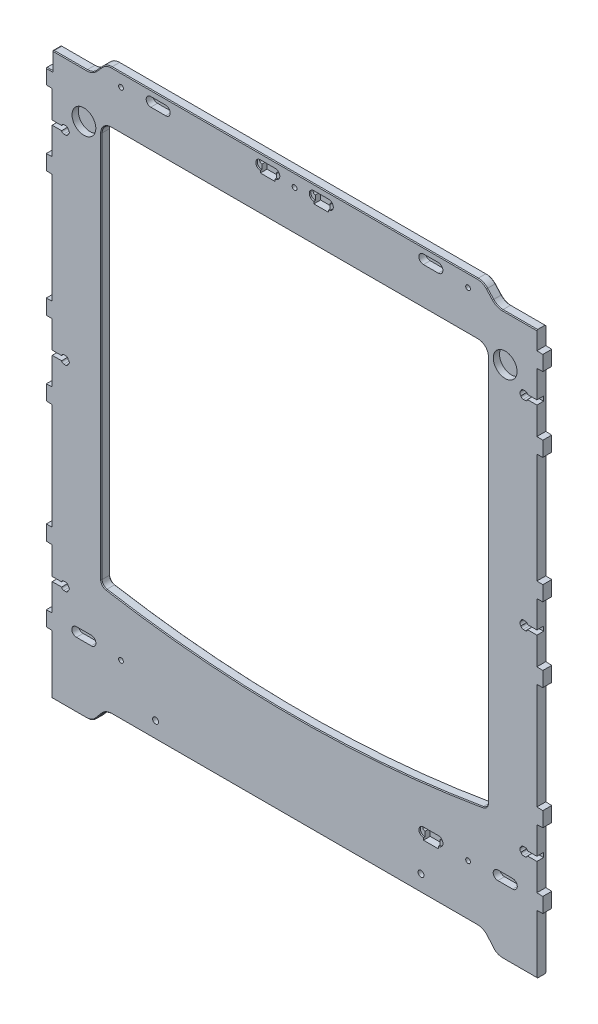
SolidWorks part; units mm, degrees
ref_plane "Alzado" through (0, 0, 0) normal (0, 0, 1) x (1, 0, 0)
ref_plane "Planta" through (0, 0, 0) normal (0, 1, 0) x (1, 0, 0)
ref_plane "Vista lateral" through (0, 0, 0) normal (1, 0, 0) x (0, 0, -1)
ref_plane "Plano1" through (0, 0, 3) normal (0, 0, 1) x (1, 0, 0)
sketch "Croquis1" plane through (0, 0, 3) normal (0, 0, 1) x (1, 0, 0)
  line L0 (167.1, -194) -> (167.1, 194)
  line L1 (167.1, 194) -> (-167.1, 194)
  line L2 (-167.1, 194) -> (-167.1, -194)
  line L3 (-167.1, -194) -> (167.1, -194)
  dimension "D1" = 334.2
  dimension "D2" = 388
extrude "Saliente-Extruir1" add sketch "Croquis1" against normal blind 6
sketch "Croquis2" plane through (0, 0, 3) normal (0, 0, 1) x (1, 0, 0)
  line L0 (96.8, -151.6) -> (96.8, -150.1)
  line L1 (96.8, -143.9) -> (86.8, -143.9)
  line L2 (86.8, -150.1) -> (86.8, -151.6)
  line L3 (86.8, -151.6) -> (96.8, -151.6)
  line L5 (-167.1, -194) -> (167.1, -194) construction
  arc A0 (96.8, -150.1) -> (96.8, -143.9) centre (96.8, -147) ccw
  arc A1 (86.8, -143.9) -> (86.8, -150.1) centre (86.8, -147) ccw
  dimension "D1" = 3.1
  dimension "D2" = 3.1
  dimension "D3" = 42.4
extrude "Cortar-Extruir1" cut sketch "Croquis2" against normal blind 1
sketch "Croquis3" plane through (0, 0, 2) normal (0, 0, 1) x (1, 0, 0)
  line L0 (86.8, -146.9) -> (86.8, -151.6)
  line L1 (86.8, -151.6) -> (96.8, -151.6)
  line L2 (96.8, -151.6) -> (96.8, -146.9)
  line L3 (96.8, -143.9) -> (86.8, -143.9)
  line L4 (96.8, -151.6) -> (96.8, -150.1) construction
  arc A0 (86.8, -143.9) -> (86.8, -146.9) centre (86.8, -145.4) ccw
  arc A1 (96.8, -146.9) -> (96.8, -143.9) centre (96.8, -145.4) ccw
  dimension "D1" = 1.5
  dimension "D2" = 10
extrude "Cortar-Extruir2" cut sketch "Croquis3" against normal blind 3.5
sketch "Croquis4" plane through (0, 0, 3) normal (0, 0, 1) x (1, 0, 0)
  line L0 (-13, 182.4) -> (-13, 183.9)
  line L1 (-13, 190.1) -> (-23, 190.1)
  line L2 (-23, 183.9) -> (-23, 182.4)
  line L3 (-23, 182.4) -> (-13, 182.4)
  line L4 (86.8, -150.1) -> (86.8, -151.6) construction
  line L5 (86.8, -151.6) -> (96.8, -151.6) construction
  arc A0 (-13, 183.9) -> (-13, 190.1) centre (-13, 187) ccw
  arc A1 (-23, 190.1) -> (-23, 183.9) centre (-23, 187) ccw
  dimension "D1" = 3.1
  dimension "D2" = 99.8
  dimension "D3" = 109.8
  dimension "D4" = 334
  dimension "D5" = 338.6
extrude "Cortar-Extruir3" cut sketch "Croquis4" against normal blind 1
sketch "Croquis5" plane through (0, 0, 2) normal (0, 0, 1) x (1, 0, 0)
  line L0 (-23, 187.1) -> (-23, 182.4)
  line L1 (-23, 182.4) -> (-13, 182.4)
  line L2 (-13, 182.4) -> (-13, 187.1)
  line L3 (-13, 190.1) -> (-23, 190.1)
  line L4 (-13, 182.4) -> (-13, 183.9) construction
  arc A0 (-23, 190.1) -> (-23, 187.1) centre (-23, 188.6) ccw
  arc A1 (-13, 187.1) -> (-13, 190.1) centre (-13, 188.6) ccw
  dimension "D1" = 1.5
  dimension "D2" = 10
extrude "Cortar-Extruir4" cut sketch "Croquis5" against normal blind 3.5
sketch "Croquis6" plane through (0, 0, -3) normal (0, 0, -1) x (-1, 0, 0)
  line L0 (167.1, 121.8397) -> (167.1, 161.5603)
  line L1 (167.1, 161.5603) -> (163.1, 161.5603)
  line L2 (163.1, 161.5603) -> (163.1, 121.8397)
  line L3 (163.1, 121.8397) -> (167.1, 121.8397)
  line L4 (167.1, 194) -> (167.1, -194) construction
  line L5 (167.1, -194) -> (-167.1, -194) construction
  dimension "D1" = 4
  dimension "D2" = 315.8397
  dimension "D3" = 355.5603
extrude "Cortar-Extruir5" cut sketch "Croquis6" against normal through all
sketch "Croquis7" plane through (0, 0, -3) normal (0, 0, -1) x (-1, 0, 0)
  line L0 (167.1, -12.3603) -> (167.1, 27.3603)
  line L1 (167.1, 27.3603) -> (163.1, 27.3603)
  line L2 (163.1, 27.3603) -> (163.1, -12.3603)
  line L3 (163.1, -12.3603) -> (167.1, -12.3603)
  line L4 (163.1, 161.5603) -> (163.1, 121.8397) construction
  line L5 (167.1, 161.5603) -> (163.1, 161.5603) construction
  dimension "D1" = 4
  dimension "D2" = 134.2
  dimension "D3" = 173.9206
extrude "Cortar-Extruir6" cut sketch "Croquis7" against normal through all
sketch "Croquis8" plane through (0, 0, -3) normal (0, 0, -1) x (-1, 0, 0)
  line L0 (167.1, -144.0603) -> (167.1, -104.3397)
  line L1 (167.1, -104.3397) -> (163.1, -104.3397)
  line L2 (163.1, -104.3397) -> (163.1, -144.0603)
  line L3 (163.1, -144.0603) -> (167.1, -144.0603)
  line L4 (167.1, 121.8397) -> (167.1, 27.3603) construction
  line L5 (163.1, 121.8397) -> (167.1, 121.8397) construction
  dimension "D1" = 4
  dimension "D2" = 226.1794
  dimension "D3" = 265.9
extrude "Cortar-Extruir7" cut sketch "Croquis8" against normal through all
sketch "Croquis9" plane through (0, 0, 3) normal (0, 0, 1) x (1, 0, 0)
  line L0 (-163.1, -125.8) -> (-156.779, -125.8)
  line L1 (-155.3, -127.05) -> (-153.9, -127.05)
  line L2 (-152.421, -125.8) -> (-152.421, -125.6375)
  line L3 (-152.421, -122.9625) -> (-152.421, -122.8)
  line L4 (-153.9, -121.55) -> (-155.3, -121.55)
  line L5 (-156.779, -122.8) -> (-163.1, -122.8)
  line L6 (-163.1, -122.8) -> (-163.1, -125.8)
  line L7 (-167.1, -144.0603) -> (-167.1, -194) construction
  line L8 (-167.1, -194) -> (167.1, -194) construction
  arc A0 (-156.779, -125.8) -> (-155.3, -127.05) centre (-155.3, -125.55) ccw
  arc A1 (-153.9, -127.05) -> (-152.421, -125.8) centre (-153.9, -125.55) ccw
  arc A2 (-152.421, -125.6375) -> (-152.421, -122.9625) centre (-153.1, -124.3) ccw
  arc A3 (-152.421, -122.8) -> (-153.9, -121.55) centre (-153.9, -123.05) ccw
  arc A4 (-155.3, -121.55) -> (-156.779, -122.8) centre (-155.3, -123.05) ccw
  dimension "D1" = 1.5
  dimension "D2" = 1.5
  dimension "D3" = 1.5
  dimension "D4" = 4
  dimension "D5" = 10.321
  dimension "D6" = 11.8
  dimension "D7" = 13.2
  dimension "D8" = 14
  dimension "D9" = 68.3625
extrude "Cortar-Extruir8" cut sketch "Croquis9" against normal blind 4.5
sketch "Croquis10" plane through (0, 0, 3) normal (0, 0, 1) x (1, 0, 0)
  line L0 (-163.1, 6.1) -> (-156.779, 6.1)
  line L1 (-155.3, 4.85) -> (-153.9, 4.85)
  line L2 (-152.421, 6.1) -> (-152.421, 6.2625)
  line L3 (-152.421, 8.9375) -> (-152.421, 9.1)
  line L4 (-153.9, 10.35) -> (-155.3, 10.35)
  line L5 (-156.779, 9.1) -> (-163.1, 9.1)
  line L6 (-163.1, 9.1) -> (-163.1, 6.1)
  line L7 (-167.1, -144.0603) -> (-167.1, -194) construction
  line L8 (-167.1, -194) -> (167.1, -194) construction
  arc A0 (-156.779, 6.1) -> (-155.3, 4.85) centre (-155.3, 6.35) ccw
  arc A1 (-153.9, 4.85) -> (-152.421, 6.1) centre (-153.9, 6.35) ccw
  arc A2 (-152.421, 6.2625) -> (-152.421, 8.9375) centre (-153.1, 7.6) ccw
  arc A3 (-152.421, 9.1) -> (-153.9, 10.35) centre (-153.9, 8.85) ccw
  arc A4 (-155.3, 10.35) -> (-156.779, 9.1) centre (-155.3, 8.85) ccw
  dimension "D1" = 1.5
  dimension "D2" = 1.5
  dimension "D3" = 1.5
  dimension "D4" = 4
  dimension "D5" = 200.2625
  dimension "D6" = 201.6
  dimension "D8" = 14
extrude "Cortar-Extruir9" cut sketch "Croquis10" against normal blind 4.5
sketch "Croquis11" plane through (0, 0, 3) normal (0, 0, 1) x (1, 0, 0)
  line L0 (-163.1, 140.2) -> (-156.779, 140.2)
  line L1 (-155.3, 138.95) -> (-153.9, 138.95)
  line L2 (-152.421, 140.2) -> (-152.421, 140.3625)
  line L3 (-152.421, 143.0375) -> (-152.421, 143.2)
  line L4 (-153.9, 144.45) -> (-155.3, 144.45)
  line L5 (-156.779, 143.2) -> (-163.1, 143.2)
  line L6 (-163.1, 143.2) -> (-163.1, 140.2)
  line L7 (-167.1, -12.3603) -> (-167.1, -104.3397) construction
  line L8 (-155.3, -127.05) -> (-153.9, -127.05) construction
  arc A0 (-156.779, 140.2) -> (-155.3, 138.95) centre (-155.3, 140.45) ccw
  arc A1 (-153.9, 138.95) -> (-152.421, 140.2) centre (-153.9, 140.45) ccw
  arc A2 (-152.421, 140.3625) -> (-152.421, 143.0375) centre (-153.1, 141.7) ccw
  arc A3 (-152.421, 143.2) -> (-153.9, 144.45) centre (-153.9, 142.95) ccw
  arc A4 (-155.3, 144.45) -> (-156.779, 143.2) centre (-155.3, 142.95) ccw
  dimension "D1" = 1.5
  dimension "D2" = 1.5
  dimension "D3" = 1.5
  dimension "D4" = 4
  dimension "D5" = 266
  dimension "D6" = 267.25
  dimension "D7" = 267.4125
  dimension "D8" = 14
  dimension "D9" = 268.75
  dimension "D10" = 270
extrude "Cortar-Extruir10" cut sketch "Croquis11" against normal blind 4.5
sketch "Croquis12" plane through (0, 0, -3) normal (0, 0, -1) x (-1, 0, 0)
  line L0 (-126.9478, -194) -> (126.9478, -194)
  line L1 (126.9478, -194) -> (126.9478, -183.0928)
  line L2 (126.9478, -183.0928) -> (-126.9478, -183.0928)
  line L3 (-126.9478, -183.0928) -> (-126.9478, -194)
  line L4 (163.1, 27.3603) -> (163.1, -12.3603) construction
  line L5 (167.1, 27.3603) -> (163.1, 27.3603) construction
  dimension "D1" = 36.1522
  dimension "D2" = 290.0478
  dimension "D3" = 210.4531
  dimension "D4" = 221.3603
extrude "Cortar-Extruir11" cut sketch "Croquis12" against normal through all
sketch "Croquis13" plane through (0, 0, -3) normal (0, 0, -1) x (-1, 0, 0)
  line L0 (-167.1, 171.8397) -> (-163.1, 171.8397)
  line L1 (-163.1, 171.8397) -> (-163.1, 194)
  line L2 (-163.1, 194) -> (-167.1, 194)
  line L3 (-167.1, 194) -> (-167.1, 171.8397)
  line L4 (167.1, -144.0603) -> (167.1, -194) construction
  line L5 (167.1, -194) -> (126.9478, -194) construction
  dimension "D1" = 330.2
  dimension "D2" = 334.2
  dimension "D3" = 365.8397
  dimension "D4" = 388
extrude "Cortar-Extruir12" cut sketch "Croquis13" against normal through all
sketch "Croquis14" plane through (0, 0, -3) normal (0, 0, -1) x (-1, 0, 0)
  line L0 (-163.1, 184) -> (-126.9478, 184)
  line L1 (-126.9478, 184) -> (-126.9478, 194)
  line L2 (-126.9478, 194) -> (-163.1, 194)
  line L3 (-163.1, 194) -> (-163.1, 184)
  line L4 (167.1, -144.0603) -> (167.1, -194) construction
  line L5 (167.1, -194) -> (126.9478, -194) construction
  dimension "D1" = 294.0478
  dimension "D2" = 330.2
  dimension "D3" = 378
  dimension "D4" = 388
extrude "Cortar-Extruir13" cut sketch "Croquis14" against normal through all
sketch "Croquis15" plane through (0, 0, -3) normal (0, 0, -1) x (-1, 0, 0)
  line L0 (126.9478, 194) -> (126.9478, 184)
  line L1 (126.9478, 184) -> (167.1, 184)
  line L2 (167.1, 184) -> (167.1, 194)
  line L3 (167.1, 194) -> (126.9478, 194)
  line L4 (167.1, -144.0603) -> (167.1, -194) construction
  line L5 (167.1, -194) -> (126.9478, -194) construction
  dimension "D1" = 40.1522
  dimension "D2" = 378
  dimension "D3" = 388
extrude "Cortar-Extruir14" cut sketch "Croquis15" against normal through all
sketch "Croquis16" plane through (0, 0, -3) normal (0, 0, -1) x (-1, 0, 0)
  line L0 (163.1, 171.8397) -> (167.1, 171.8397)
  line L1 (167.1, 171.8397) -> (167.1, 184)
  line L2 (167.1, 184) -> (163.1, 184)
  line L3 (163.1, 184) -> (163.1, 171.8397)
  line L4 (-167.1, -194) -> (-167.1, 171.8397) construction
  line L5 (-126.9478, -194) -> (-167.1, -194) construction
  dimension "D1" = 330.2
  dimension "D2" = 334.2
  dimension "D3" = 365.8397
  dimension "D4" = 378
extrude "Cortar-Extruir15" cut sketch "Croquis16" against normal through all
sketch "Croquis17" plane through (0, 0, -3) normal (0, 0, -1) x (-1, 0, 0)
  line L0 (167.1, 37.6397) -> (167.1, 111.5603)
  line L1 (167.1, 111.5603) -> (163.1, 111.5603)
  line L2 (163.1, 111.5603) -> (163.1, 37.6397)
  line L3 (163.1, 37.6397) -> (167.1, 37.6397)
  line L4 (-167.1, -194) -> (-167.1, 171.8397) construction
  line L5 (-126.9478, -194) -> (-167.1, -194) construction
  dimension "D1" = 330.2
  dimension "D2" = 334.2
  dimension "D3" = 231.6397
  dimension "D4" = 305.5603
extrude "Cortar-Extruir16" cut sketch "Croquis17" against normal through all
sketch "Croquis18" plane through (0, 0, -3) normal (0, 0, -1) x (-1, 0, 0)
  line L0 (167.1, -94.0603) -> (167.1, -22.6397)
  line L1 (167.1, -22.6397) -> (163.1, -22.6397)
  line L2 (163.1, -22.6397) -> (163.1, -94.0603)
  line L3 (163.1, -94.0603) -> (167.1, -94.0603)
  line L4 (167.1, 171.8397) -> (167.1, 161.5603) construction
  line L5 (-126.9478, 194) -> (126.9478, 194) construction
  dimension "D1" = 4
  dimension "D2" = 216.6397
  dimension "D3" = 288.0603
extrude "Cortar-Extruir17" cut sketch "Croquis18" against normal through all
sketch "Croquis19" plane through (0, 0, -3) normal (0, 0, -1) x (-1, 0, 0)
  line L0 (167.1, -154.3397) -> (163.1, -154.3397)
  line L1 (163.1, -154.3397) -> (163.1, -194)
  line L2 (163.1, -194) -> (167.1, -194)
  line L3 (167.1, -194) -> (167.1, -154.3397)
  line L4 (167.1, 171.8397) -> (167.1, 161.5603) construction
  line L5 (163.1, 171.8397) -> (167.1, 171.8397) construction
  dimension "D1" = 4
  dimension "D2" = 326.1794
  dimension "D3" = 365.8397
extrude "Cortar-Extruir18" cut sketch "Croquis19" against normal through all
sketch "Croquis24" plane through (0, 0, -3) normal (0, 0, -1) x (-1, 0, 0)
  line L0 (130, 158.5) -> (-130, 158.5)
  line L1 (-130, 158.5) -> (-130, -111.6474)
  line L2 (130, -111.6474) -> (130, 158.5)
  line L3 (167.1, -144.0603) -> (167.1, -154.3397) construction
  line L4 (163.1, -194) -> (126.9478, -194) construction
  arc A0 (-130, -111.6474) -> (130, -111.6474) centre (0, 627) ccw
  dimension "D1" = 750
  dimension "D2" = 37.1
  dimension "D3" = 167.1
  dimension "D4" = 82.3526
  dimension "D5" = 352.5
extrude "Cortar-Extruir23" cut sketch "Croquis24" against normal through all
sketch "Croquis25" plane through (0, 0, 3) normal (0, 0, 1) x (1, 0, 0)
  line L0 (-86.75, 190.1) -> (-96.75, 190.1)
  line L1 (-96.75, 183.9) -> (-86.75, 183.9)
  line L2 (167.1, -194) -> (167.1, 171.8397) construction
  line L3 (126.9478, -194) -> (167.1, -194) construction
  arc A0 (-96.75, 190.1) -> (-96.75, 183.9) centre (-96.75, 187) ccw
  arc A1 (-86.75, 183.9) -> (-86.75, 190.1) centre (-86.75, 187) ccw
  dimension "D1" = 3.1
  dimension "D2" = 253.85
  dimension "D3" = 263.85
  dimension "D4" = 381
extrude "Cortar-Extruir24" cut sketch "Croquis25" against normal blind 4.5
sketch "Croquis26" plane through (0, 0, 3) normal (0, 0, 1) x (1, 0, 0)
  line L0 (-146.8, -150.1) -> (-136.8, -150.1)
  line L1 (-136.8, -143.9) -> (-146.8, -143.9)
  line L2 (167.1, -194) -> (167.1, 171.8397) construction
  line L3 (126.9478, -194) -> (167.1, -194) construction
  arc A0 (-136.8, -150.1) -> (-136.8, -143.9) centre (-136.8, -147) ccw
  arc A1 (-146.8, -143.9) -> (-146.8, -150.1) centre (-146.8, -147) ccw
  dimension "D1" = 3.1
  dimension "D2" = 303.9
  dimension "D3" = 313.9
  dimension "D4" = 47
extrude "Cortar-Extruir25" cut sketch "Croquis26" against normal blind 4.5
mirror "Simetría1" about plane through (0, 0, 0) normal (1, 0, 0) of "Cortar-Extruir9", "Cortar-Extruir3", "Cortar-Extruir4", "Cortar-Extruir5", "Cortar-Extruir6", "Cortar-Extruir7", "Cortar-Extruir8", "Cortar-Extruir10", "Cortar-Extruir16", "Cortar-Extruir17", "Cortar-Extruir18", "Cortar-Extruir24", "Cortar-Extruir25"
draft "Ángulo de salida1" type of draft neutral plane draft angle 2 faces to draft 1 face at (165.1, -154.3397, 0) neutral plane through (163.1, -154.3397, 3) neutral plane normal (1, 0, 0) parameters "D1"=2
draft "Ángulo de salida2" type of draft neutral plane draft angle 2 faces to draft 1 face at (165.1, 171.8397, 0) neutral plane through (163.1, 171.8397, 3) neutral plane normal (1, 0, 0) parameters "D1"=2
draft "Ángulo de salida3" type of draft neutral plane draft angle 2 faces to draft 1 face at (-165.1, 171.8397, 0) neutral plane through (-163.1, 184, 3) neutral plane normal (-1, 0, 0) parameters "D1"=2
draft "Ángulo de salida4" type of draft neutral plane draft angle 2 faces to draft 1 face at (-165.1, -154.3397, 0) neutral plane through (-163.1, -154.3397, 3) neutral plane normal (-1, 0, 0) parameters "D1"=2
draft "Ángulo de salida5" type of draft neutral plane draft angle 2 faces to draft 2 face at (165.1, -22.6397, 0) face at (165.1, -94.0603, 0) neutral plane through (163.1, -22.6397, 3) neutral plane normal (1, 0, 0) parameters "D1"=2
draft "Ángulo de salida6" type of draft neutral plane draft angle 2 faces to draft 2 face at (165.1, 111.5603, 0) face at (165.1, 37.6397, 0) neutral plane through (163.1, 111.5603, 3) neutral plane normal (1, 0, 0) parameters "D1"=2
draft "Ángulo de salida7" type of draft neutral plane draft angle 2 faces to draft 2 face at (-165.1, 37.6397, 0) face at (-165.1, 111.5603, 0) neutral plane through (-163.1, 111.5603, 3) neutral plane normal (-1, 0, 0) parameters "D1"=2
draft "Ángulo de salida8" type of draft neutral plane draft angle 2 faces to draft 2 face at (-165.1, -94.0603, 0) face at (-165.1, -22.6397, 0) neutral plane through (-163.1, -22.6397, 3) neutral plane normal (-1, 0, 0) parameters "D1"=2
draft "Ángulo de salida9" type of draft neutral plane draft angle 2 faces to draft 2 face at (165.1, -104.3397, 0) face at (165.1, -144.0603, 0) neutral plane through (163.1, -104.3397, 3) neutral plane normal (1, 0, 0) parameters "D1"=2
draft "Ángulo de salida10" type of draft neutral plane draft angle 2 faces to draft 2 face at (165.1, -12.3603, 0) face at (165.1, 27.3603, 0) neutral plane through (163.1, 27.3603, 3) neutral plane normal (1, 0, 0) parameters "D1"=2
draft "Ángulo de salida11" type of draft neutral plane draft angle 2 faces to draft 2 face at (165.1, 161.5603, 0) face at (165.1, 121.8397, 0) neutral plane through (163.1, 161.5603, 3) neutral plane normal (1, 0, 0) parameters "D1"=2
draft "Ángulo de salida12" type of draft neutral plane draft angle 42.465 faces to draft 2 face at (126.9478, 189, 0) face at (-126.9478, 189, 0) neutral plane through (167.1, 194, -3) neutral plane normal (0, 1, 0) parameters "D1"=42.465
draft "Ángulo de salida13" type of draft neutral plane draft angle 2 faces to draft 2 face at (-165.1, 121.8397, 0) face at (-165.1, 161.5603, 0) neutral plane through (-163.1, 161.5603, 3) neutral plane normal (-1, 0, 0) parameters "D1"=2
draft "Ángulo de salida14" type of draft neutral plane draft angle 2 faces to draft 2 face at (-165.1, 27.3603, 0) face at (-165.1, -12.3603, 0) neutral plane through (-163.1, 27.3603, 3) neutral plane normal (-1, 0, 0) parameters "D1"=2
draft "Ángulo de salida15" type of draft neutral plane draft angle 2 faces to draft 2 face at (-165.1, -144.0603, 0) face at (-165.1, -104.3397, 0) neutral plane through (-163.1, -104.3397, 3) neutral plane normal (-1, 0, 0) parameters "D1"=2
draft "Ángulo de salida16" type of draft neutral plane draft angle 40 faces to draft 2 face at (126.9478, -188.5464, 0) face at (-126.9478, -188.5464, 0) neutral plane through (-126.9478, -183.0928, 3) neutral plane normal (0, -1, 0) parameters "D1"=40
hole_wizard "Diámetro de taladro Ø3.2 (3.2)1" positions "Croquis29" profile "Croquis28" hole size "Ø3.2" standard "Ansi Metric"
sketch "Croquis29" plane through (0, 0, -3) normal (0, 0, -1) x (-1, 0, 0)
  point P0 (-116.8, -148.55)
  point P1 (-116.8, 185.45)
sketch "Croquis28" plane through (116.8, -148.55, -3) normal (1, 0, 0) x (0, 1, 0)
  line L0 (0, 0) -> (0, 6)
  line L1 (0, 6) -> (1.6, 6)
  line L2 (1.6, 6) -> (1.6, 0)
  line L5 (1.6, 0) -> (0, 0)
  line L11 (0, -6.35) -> (0, 107.95) construction
  dimension "Diámetro de taladro hasta el siguiente" = 3.2
  dimension "Profundidad de taladro hasta el siguiente" = 6
hole_wizard "Diámetro de taladro Ø3.2 (3.2)2" positions "Croquis31" profile "Croquis30" hole size "Ø3.2" standard "Ansi Metric"
sketch "Croquis31" plane through (0, 0, 3) normal (0, 0, 1) x (1, 0, 0)
  point P0 (-116.8, -148.55)
  point P1 (-116.8, 185.45)
sketch "Croquis30" plane through (-116.8, -148.55, 3) normal (1, 0, 0) x (0, -1, 0)
  line L0 (0, 0) -> (0, 6)
  line L1 (0, 6) -> (1.6, 6)
  line L2 (1.6, 6) -> (1.6, 0)
  line L5 (1.6, 0) -> (0, 0)
  line L11 (0, -6.35) -> (0, 107.95) construction
  dimension "Diámetro de taladro hasta el siguiente" = 3.2
  dimension "Profundidad de taladro hasta el siguiente" = 6
hole_wizard "Diámetro de taladro Ø3.2 (3.2)3" positions "Croquis35" profile "Croquis34" hole size "Ø3.2" standard "Ansi Metric"
sketch "Croquis35" plane through (0, 0, 3) normal (0, 0, 1) x (1, 0, 0)
  point P0 (0, 185.45)
sketch "Croquis34" plane through (0, 185.45, 3) normal (1, 0, 0) x (0, -1, 0)
  line L0 (0, 0) -> (0, 4.5)
  line L1 (0, 4.5) -> (1.6, 4.5)
  line L2 (1.6, 4.5) -> (1.6, 0)
  line L5 (1.6, 0) -> (0, 0)
  line L10 (0, 4.5) -> (-1.6, 4.5) construction
  line L11 (0, -6.35) -> (0, 107.95) construction
  dimension "Diámetro de taladro" = 3.2
  dimension "Profundidad de taladro" = 4.5
  dimension "Ángulo de perforador" = 180
hole_wizard "Diámetro de taladro Ø16.0 (16)1" positions "Croquis37" profile "Croquis36" hole size "Ø16.0" standard "Ansi Metric"
sketch "Croquis37" plane through (0, 0, 3) normal (0, 0, 1) x (1, 0, 0)
  point P0 (141.75, 153)
  point P1 (-141.75, 153)
sketch "Croquis36" plane through (141.75, 153, 3) normal (1, 0, 0) x (0, -1, 0)
  line L0 (0, 0) -> (0, 4.2)
  line L1 (0, 4.2) -> (8, 4.2)
  line L2 (8, 4.2) -> (8, 0)
  line L5 (8, 0) -> (0, 0)
  line L10 (0, 4.2) -> (-8, 4.2) construction
  line L11 (0, -6.35) -> (0, 107.95) construction
  dimension "Diámetro de taladro" = 16
  dimension "Profundidad de taladro" = 4.2
  dimension "Ángulo de perforador" = 180
hole_wizard "Diámetro de taladro Ø4.0 (4)1" positions "Croquis39" profile "Croquis38" hole size "Ø4.0" standard "Ansi Metric"
sketch "Croquis39" plane through (0, 0, 3) normal (0, 0, 1) x (1, 0, 0)
  point P0 (-93.5, -172)
  point P1 (85.1, -172)
sketch "Croquis38" plane through (-93.5, -172, 3) normal (1, 0, 0) x (0, -1, 0)
  line L0 (0, 0) -> (0, 4.5)
  line L1 (0, 4.5) -> (2, 4.5)
  line L2 (2, 4.5) -> (2, 0)
  line L5 (2, 0) -> (0, 0)
  line L10 (0, 4.5) -> (-2, 4.5) construction
  line L11 (0, -6.35) -> (0, 107.95) construction
  dimension "Diámetro de taladro" = 4
  dimension "Profundidad de taladro" = 4.5
  dimension "Ángulo de perforador" = 180
fillet "Redondeo1" radius 1 1 edges at (-163.1, 184, 0) tangent propagation no
fillet "Redondeo3" radius 4 2 edges at (-130, -111.6474, 0) (130, -111.6474, 0) tangent propagation no
fillet "Redondeo4" radius 6.5 2 edges at (130, 158.5, 0) (-130, 158.5, 0) tangent propagation no
fillet "Redondeo5" radius 8.5 8 edges at (126.9478, -183.0928, 0) (136.1, 184, 0) (126.9478, 194, 0) (-136.1, -194, 0) (136.1, -194, 0) (-136.1, 184, 0) (-126.9478, -183.0928, 0) (-126.9478, 194, 0) tangent propagation no
chamfer "Chaflán1" distance 0.5 angle 45 58 edges at (151.4716, 184, -3) (136.4175, 184.7209, -3) (131.5239, 189, -3) (126.6303, 193.2791, -3) (0, 194, -3) (-165.1, 171.7698, -3) (-126.6303, 193.2791, -3) (-131.5239, 189, -3) (-163.1, 177.4198, -3) (-136.4175, 184.7209, -3) (-162.8071, 183.7071, -3) (-150.9716, 184, -3) (151.4716, 184, 3) (136.4175, 184.7209, 3) (131.5239, 189, 3) (126.6303, 193.2791, 3) (0, 194, 3) (-126.6303, 193.2791, 3) (-131.5239, 189, 3) (-136.4175, 184.7209, 3) (-150.9716, 184, 3) (-165.1, 171.7698, 3) (-162.8071, 183.7071, 3) (-163.1, 177.4198, 3) (-151.5818, -194, 3) (-136.4714, -193.2036, 3) (-131.5239, -188.5464, 3) (-126.5764, -183.8892, 3) (0, -183.0928, 3) (126.5764, -183.8892, 3) (131.5239, -188.5464, 3) (136.4714, -193.2036, 3) (151.5818, -194, 3) (-151.5818, -194, -3) (-136.4714, -193.2036, -3) (151.5818, -194, -3) (-131.5239, -188.5464, -3) (136.4714, -193.2036, -3) (-126.5764, -183.8892, -3) (131.5239, -188.5464, -3) (0, -183.0928, -3) (126.5764, -183.8892, -3) (0, 158.5, 3) (128.0962, 156.5962, 3) (-128.0962, 156.5962, 3) (130, 21.8589, 3) (-130, 21.8589, 3) (129.058, -110.8608, 3) (-129.058, -110.8608, 3) (0, -123, 3) (128.0962, 156.5962, -3) (0, 158.5, -3) (130, 21.8589, -3) (-128.0962, 156.5962, -3) (129.058, -110.8608, -3) (-130, 21.8589, -3) (0, -123, -3) (-129.058, -110.8608, -3)
